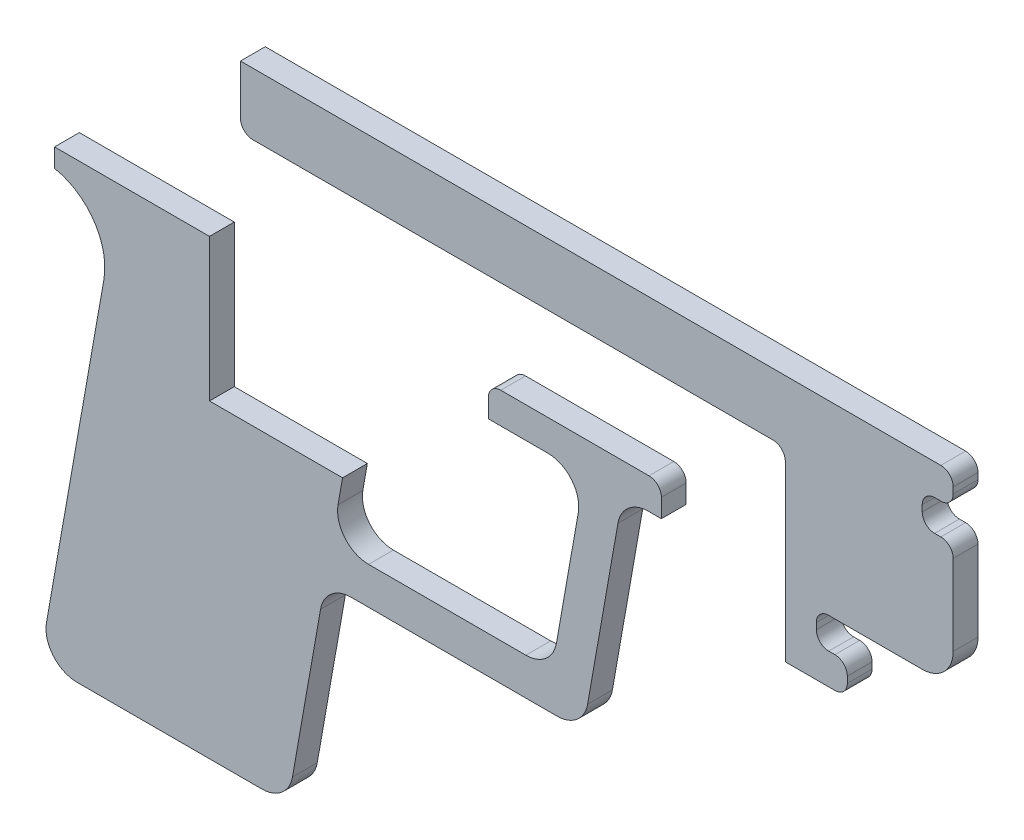
SolidWorks part; units mm, degrees
ref_plane "Front Plane" through (0, 0, 0) normal (0, 0, 1) x (1, 0, 0)
ref_plane "Top Plane" through (0, 0, 0) normal (0, 1, 0) x (1, 0, 0)
ref_plane "Right Plane" through (0, 0, 0) normal (1, 0, 0) x (0, 0, -1)
sketch "Sketch1" plane through (0, 0, 0) normal (0, 0, 1) x (1, 0, 0)
  line L0 (10, 0) -> (-2.3429, -70)
  line L1 (0, 0) -> (10, 0)
  line L2 (0, 0) -> (0, 30)
  line L3 (0, 30) -> (145, 30)
  line L4 (145, 0) -> (145, 20)
  line L5 (-2.3429, -70) -> (37.6571, -70)
  line L6 (37.6571, -70) -> (43.6522, -36)
  line L7 (44.7102, -30) -> (80.2501, -30)
  line L8 (145, 25) -> (140, 25)
  line L10 (145, 20) -> (140, 20)
  line L11 (140, 25) -> (140, 20)
  line L12 (80.2501, -30) -> (85.5399, 0)
  line L13 (43.6522, -36) -> (85.2847, -36)
  line L14 (85.2847, -36) -> (91.6325, 0)
  line L15 (85.2847, -36) -> (91.4488, -1.0419) construction
  line L16 (44.7102, -36) -> (85.2847, -36) construction
  line L17 (44.7102, -30) -> (50, 0)
  line L18 (50, 0) -> (85.5399, 0)
  line L19 (91.6325, 0) -> (145, 0)
  line L20 (145, 25) -> (145, 30)
  dimension "D1" = 145
  dimension "D2" = 30
  dimension "D3" = 80
  dimension "D4" = 10
  dimension "D5" = 40
  dimension "D6" = 5
  dimension "D7" = 5
  dimension "D8" = 5
  dimension "D10" = 35
  dimension "D11" = 30
  dimension "D12" = 70
  dimension "D9" = 6
extrude "Boss-Extrude1" add sketch "Sketch1" along normal blind 4
fillet "Fillet1" radius 10 1 edges at (10, 0, 2)
fillet "Fillet2" radius 5 10 edges at (-2.3429, -70, 2) (37.6571, -70, 2) (50, 0, 2) (44.7102, -30, 2) (43.6522, -36, 2) (85.5399, 0, 2) (91.6325, 0, 2) (80.2501, -30, 2) (85.2847, -36, 2) (145, 0, 2)
sketch "Sketch2" plane through (0, 0, 4) normal (0, 0, 1) x (1, 0, 0)
  line L0 (4, 30) -> (4, 0.7222) construction
  line L1 (145, 30) -> (0, 30) construction
  line L2 (0, 27) -> (4, 27)
  line L3 (0, 30) -> (0, 0) construction
  line L4 (4, 27) -> (0, 23)
  line L5 (0, 23) -> (0, 27)
  dimension "D1" = 4
  dimension "D2" = 4
  dimension "D3" = 3
extrude "Cut-Extrude1" cut sketch "Sketch2" against normal blind 4
pattern_linear "LPattern1" count 6 spacing 4 along (0, -1, 0) of "Cut-Extrude1"
fillet "Fillet3" radius 2 4 edges at (145, 20, 2) (145, 25, 2) (140, 25, 2) (140, 20, 2)
fillet "Fillet4" radius 2 1 edges at (145, 30, 2)
sketch "Sketch3" plane through (0, 0, 4) normal (0, 0, 1) x (1, 0, 0)
  line L0 (117.914, 0) -> (117.914, -10)
  line L1 (95.828, 0) -> (140, 0) construction
  line L2 (117.914, -10) -> (127.914, -10)
  line L3 (127.914, -10) -> (127.914, -5)
  line L4 (127.914, -5) -> (122.914, -5)
  line L5 (122.914, -5) -> (122.914, 0)
  line L6 (117.914, 0) -> (122.914, 0)
  dimension "D1" = 5
  dimension "D2" = 5
  dimension "D3" = 5
  dimension "D4" = 10
extrude "Boss-Extrude2" add sketch "Sketch3" against normal blind 4
fillet "Fillet5" radius 2 4 edges at (127.914, -10, 2) (127.914, -5, 2) (122.914, -5, 2) (122.914, 0, 2)
sketch "Sketch4" plane through (0, 0, 4) normal (0, 0, 1) x (1, 0, 0)
  line L0 (117.914, 0) -> (117.914, 20)
  line L1 (117.914, 20) -> (30, 20)
  line L2 (30, 20) -> (30, 30)
  line L3 (143, 30) -> (0, 30) construction
  line L4 (30, 30) -> (0, 30)
  line L5 (0, 30) -> (0, 3)
  line L6 (0, 3) -> (25, 3)
  line L7 (25, 3) -> (25, -20)
  line L8 (25, -20) -> (70, -20)
  line L9 (70, -20) -> (70, 5)
  line L10 (70, 5) -> (97.914, 5)
  line L11 (97.914, 5) -> (97.914, 0)
  line L12 (95.828, 0) -> (117.914, 0) construction
  line L13 (97.914, 0) -> (117.914, 0)
  line L14 (79.5812, 0) -> (54.1955, 0) construction
  dimension "D1" = 20
  dimension "D2" = 20
  dimension "D3" = 5
  dimension "D4" = 30
  dimension "D5" = 15
  dimension "D6" = 70
  dimension "D7" = 25
extrude "Cut-Extrude2" cut sketch "Sketch4" against normal blind 4
fillet "Fillet6" radius 2 1 edges at (117.914, 20, 2)
fillet "Fillet7" radius 2 1 edges at (97.914, 5, 2)
fillet "Fillet8" radius 2 1 edges at (30, 20, 2)
fillet "Fillet9" radius 2 1 edges at (70, 5, 2)
